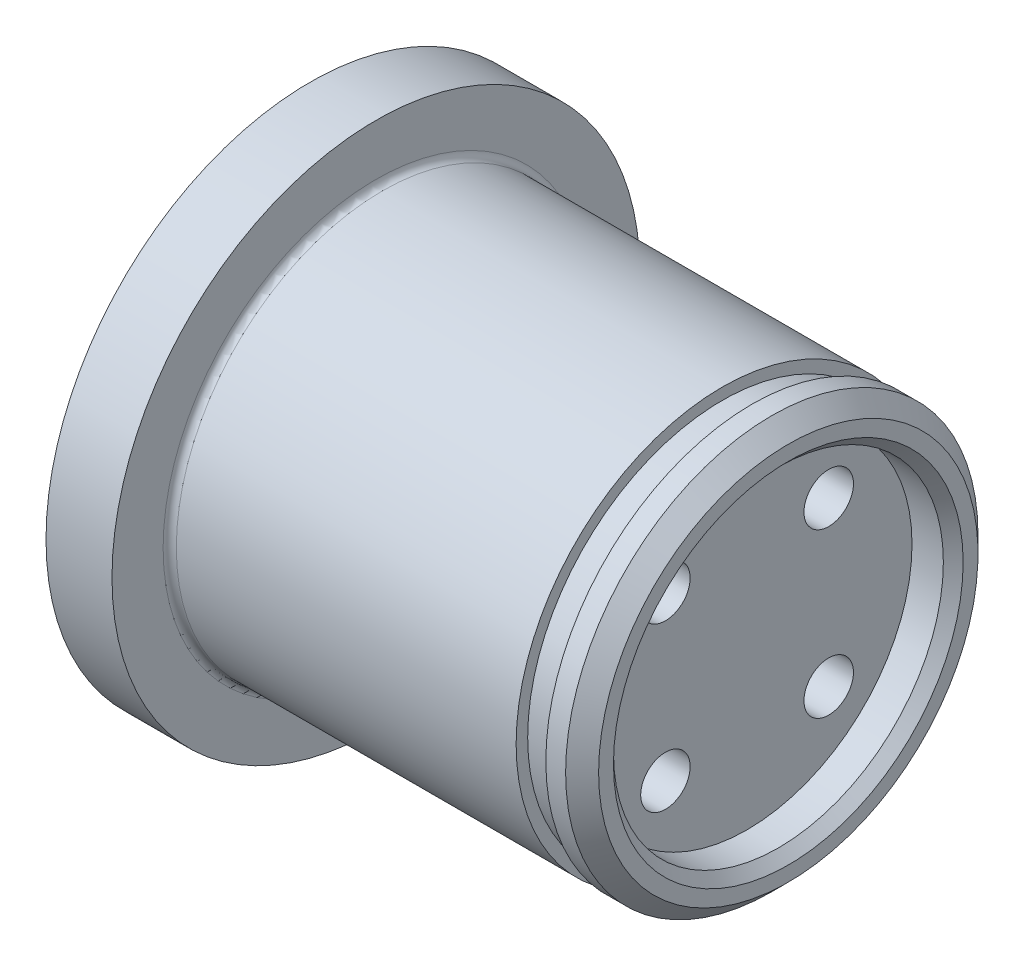
SolidWorks part; units mm, degrees
material "1060 Сплав"
ref_plane "Спереди" through (0, 0, 0) normal (0, 0, 1) x (1, 0, 0)
ref_plane "Сверху" through (0, 0, 0) normal (0, 1, 0) x (1, 0, 0)
ref_plane "Справа" through (0, 0, 0) normal (1, 0, 0) x (0, 0, -1)
sketch "Эскиз1" plane through (0, 0, 0) normal (0, 0, 1) x (1, 0, 0)
  line L0 (0, 0) -> (22138.4448, 0) construction
  line L1 (0, 0) -> (0, 12.5)
  line L2 (0, 12.5) -> (-25, 12.5)
  line L3 (-25, 12.5) -> (-25, 16)
  line L4 (-25, 16) -> (-29, 16)
  line L5 (-29, 16) -> (-29, 0)
  line L8 (0, 0) -> (-29, 0)
  dimension "D1" = 29
  dimension "D2" = 4
  dimension "D3" = 25
  dimension "D6" = 32
revolve "Повернуть1" add sketch "Эскиз1" angle 360 about L0
sketch "Эскиз2" plane through (0, 0, 0) normal (0, 0, 1) x (1, 0, 0)
  line L0 (-4, 12.5) -> (-4, 11.8)
  line L1 (0, 12.5) -> (-25, 12.5) construction
  line L2 (-4, 11.8) -> (-2.2, 11.8)
  line L3 (-2.2, 11.8) -> (-2.2, 12.5)
  line L4 (-2.2, 12.5) -> (-4, 12.5)
  line L5 (0, -12.5) -> (0, 12.5) construction
  line L6 (0, 0) -> (-50000, 0) construction
  point P10 (-2.2, 12.15)
  point P13 (0, 0)
  dimension "D1" = 4
  dimension "D2" = 1.8
  dimension "D3" = 23.6
revolve "Вырез-Повернуть1" cut sketch "Эскиз2" angle 360 about L6
chamfer "Фаска1" distance 1 angle 45 1 edges at (0, 0, 12.5)
fillet "Скругление1" radius 0.4 1 edges at (-25, 0, 12.5)
hole_wizard "Отверстие1" positions "Эскиз3" profile "Эскиз4" legacy end condition through all
sketch "Эскиз3" plane through (0, 0, 0) normal (1, 0, 0) x (0, 0, -1)
  line L0 (0, 0) -> (0, 7) construction
  line L2 (0, 0) -> (4.9497, 4.9497) construction
  circle A0 centre (0, 0) radius 7 construction
  point P0 (4.9497, 4.9497)
  dimension "D1" = 14
  dimension "D2" = 45
sketch "Эскиз4" plane through (0, 4.9497, -4.9497) normal (0, 1, 0) x (0, 0, -1)
  line L0 (0, 0) -> (0, 29)
  line L1 (0, 29) -> (1.5, 29)
  line L2 (1.5, 29) -> (1.5, 0)
  line L3 (1.5, 0) -> (0, 0)
  line L4 (0, 110) -> (0, -10) construction
  dimension "Диаметр" = 3
  dimension "Глубина" = 29
pattern_circular "Круговой массив1" count 4 over 360 about axis through (0, 0, 0) along (-1, 0, 0) of "Отверстие1"
sketch "Эскиз5" plane through (0, 0, 0) normal (0, 0, 1) x (1, 0, 0)
  line L0 (0, 0) -> (0, 10)
  line L1 (0, -11.5) -> (0, 11.5) construction
  line L7 (0, 10) -> (-2.5, 10)
  line L8 (-2.5, 10) -> (-2.5, 0)
  line L9 (-2.5, 0) -> (0, 0)
  line L10 (0, 0) -> (-50000, 0) construction
  dimension "D1" = 2.5
  dimension "D2" = 20
revolve "Вырез-Повернуть2" cut sketch "Эскиз5" angle 360 about L10
chamfer "Фаска2" distance 0.6 angle 45 1 edges at (0, 0, -10)
